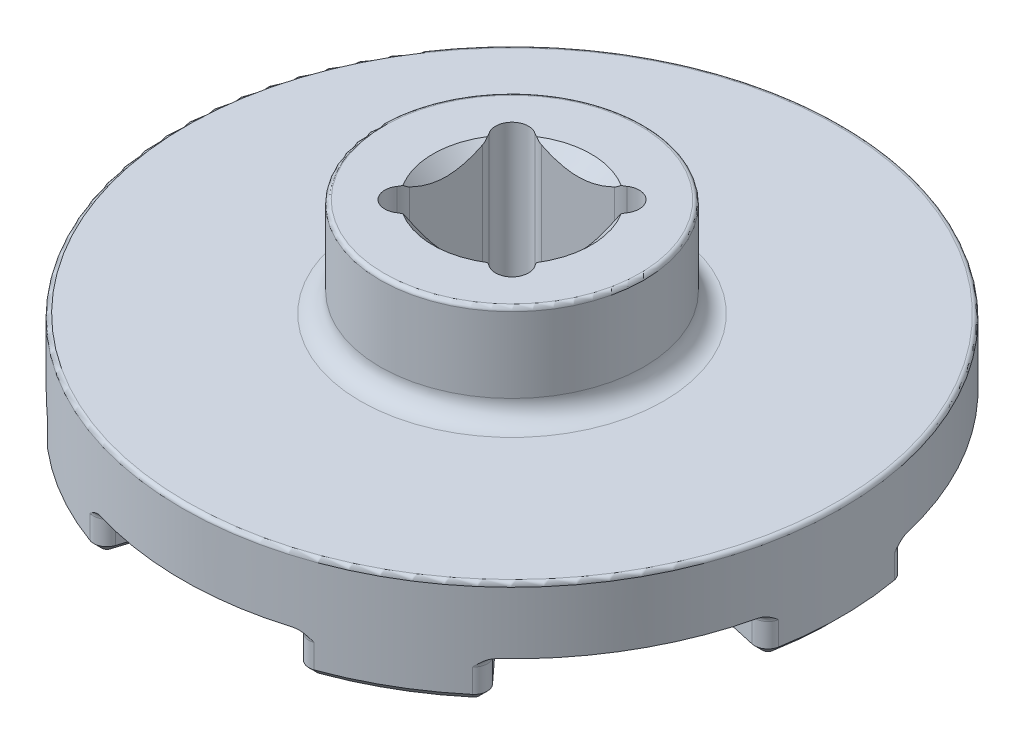
SolidWorks part; units mm, degrees
material "AISI Type S7 Tool Steel"
ref_plane "Front Plane" through (0, 0, 0) normal (0, 0, 1) x (1, 0, 0)
ref_plane "Top Plane" through (0, 0, 0) normal (0, 1, 0) x (1, 0, 0)
ref_plane "Right Plane" through (0, 0, 0) normal (1, 0, 0) x (0, 0, -1)
sketch "Sketch1" plane through (0, 0, 0) normal (0, 0, 1) x (1, 0, 0)
  line L0 (6.35, 31.75) -> (6.35, 0)
  line L1 (6.35, 0) -> (9.525, 0)
  line L2 (9.525, 0) -> (9.525, 15.875)
  line L3 (9.525, 15.875) -> (31.75, 15.875)
  line L4 (31.75, 15.875) -> (31.75, 22.225)
  line L5 (31.75, 22.225) -> (12.7, 22.225)
  line L6 (12.7, 22.225) -> (12.7, 31.75)
  line L7 (12.7, 31.75) -> (6.35, 31.75)
  line L8 (0, 0) -> (0, 31.75) construction
  dimension "D1" = 6.35
  dimension "D2" = 9.525
  dimension "D3" = 31.75
  dimension "D4" = 6.35
  dimension "D5" = 6.35
  dimension "D6" = 15.875
  dimension "D7" = 31.75
revolve "Revolve1" add sketch "Sketch1" angle 360 about L8
chamfer "Chamfer1" distance 1.27 angle 45 1 edges at (0, 31.75, -6.35)
sketch "Sketch3" plane through (0, 15.875, 0) normal (0, -1, 0) x (1, 0, 0)
  line L0 (0, 0) -> (15.875, 27.4963) construction
  line L1 (9.1576, 29.044) -> (3.7808, 11.9911)
  line L2 (8.4942, 9.2698) -> (20.5741, 22.4527)
  line L3 (3.7808, 11.9911) -> (8.4942, 9.2698) construction
  line L4 (0, 0) -> (0, 31.75) construction
  line L5 (9.5474, 30.2805) -> (21.45, 23.4086) construction
  line L8 (29.7317, 6.5914) -> (12.275, 2.7213)
  line L9 (12.275, -2.7213) -> (29.7317, -6.5914)
  line L10 (0, 0) -> (31.75, 0) construction
  line L13 (12.275, 2.7213) -> (12.275, -2.7213) construction
  line L14 (0, 0) -> (27.4963, 15.875) construction
  line L15 (30.9974, 6.872) -> (30.9974, -6.872) construction
  line L18 (20.5741, -22.4527) -> (8.4942, -9.2698)
  line L19 (3.7808, -11.9911) -> (9.1576, -29.044)
  line L20 (0, 0) -> (15.875, -27.4963) construction
  line L21 (8.4942, -9.2698) -> (3.7808, -11.9911) construction
  line L22 (0, 0) -> (27.4963, -15.875) construction
  line L23 (21.45, -23.4086) -> (9.5474, -30.2805) construction
  line L24 (-9.1576, -29.044) -> (-3.7808, -11.9911)
  line L25 (-8.4942, -9.2698) -> (-20.5741, -22.4527)
  line L26 (0, 0) -> (-15.875, -27.4963) construction
  line L27 (-3.7808, -11.9911) -> (-8.4942, -9.2698) construction
  line L28 (0, 0) -> (0, -31.75) construction
  line L29 (-9.5474, -30.2805) -> (-21.45, -23.4086) construction
  line L30 (-29.7317, -6.5914) -> (-12.275, -2.7213)
  line L31 (-12.275, 2.7213) -> (-29.7317, 6.5914)
  line L32 (0, 0) -> (-31.75, 0) construction
  line L33 (-12.275, -2.7213) -> (-12.275, 2.7213) construction
  line L34 (0, 0) -> (-27.4963, -15.875) construction
  line L35 (-30.9974, -6.872) -> (-30.9974, 6.872) construction
  line L36 (-20.5741, 22.4527) -> (-8.4942, 9.2698)
  line L37 (-3.7808, 11.9911) -> (-9.1576, 29.044)
  line L38 (0, 0) -> (-15.875, 27.4963) construction
  line L39 (-8.4942, 9.2698) -> (-3.7808, 11.9911) construction
  line L40 (0, 0) -> (-27.4963, 15.875) construction
  line L41 (-21.45, 23.4086) -> (-9.5474, 30.2805) construction
  line L42 (0, 0) -> (8.4942, 9.2698) construction
  arc A0 (20.456, 24.282) -> (10.8008, 29.8564) centre (0, 0) ccw
  arc A1 (8.4942, 9.2698) -> (3.7808, 11.9911) centre (0, 0) ccw
  circle A2 centre (0, 0) radius 31.75 construction
  arc A3 (20.456, 24.282) -> (20.5741, 22.4527) centre (19.6378, 23.3107) cw
  arc A4 (9.1576, 29.044) -> (10.8008, 29.8564) centre (10.3688, 28.6622) cw
  arc A17 (31.2568, -5.5744) -> (31.2568, 5.5744) centre (0, 0) ccw
  arc A18 (12.275, -2.7213) -> (12.275, 2.7213) centre (0, 0) ccw
  arc A19 (31.2568, -5.5744) -> (29.7317, -6.5914) centre (30.0065, -5.3515) cw
  arc A20 (29.7317, 6.5914) -> (31.2568, 5.5744) centre (30.0065, 5.3515) cw
  arc A21 (10.8008, -29.8564) -> (20.456, -24.282) centre (0, 0) ccw
  arc A22 (3.7808, -11.9911) -> (8.4942, -9.2698) centre (0, 0) ccw
  arc A23 (10.8008, -29.8564) -> (9.1576, -29.044) centre (10.3688, -28.6622) cw
  arc A24 (20.5741, -22.4527) -> (20.456, -24.282) centre (19.6378, -23.3107) cw
  arc A25 (-20.456, -24.282) -> (-10.8008, -29.8564) centre (0, 0) ccw
  arc A26 (-8.4942, -9.2698) -> (-3.7808, -11.9911) centre (0, 0) ccw
  arc A27 (-20.456, -24.282) -> (-20.5741, -22.4527) centre (-19.6378, -23.3107) cw
  arc A28 (-9.1576, -29.044) -> (-10.8008, -29.8564) centre (-10.3688, -28.6622) cw
  arc A29 (-31.2568, 5.5744) -> (-31.2568, -5.5744) centre (0, 0) ccw
  arc A30 (-12.275, 2.7213) -> (-12.275, -2.7213) centre (0, 0) ccw
  arc A31 (-31.2568, 5.5744) -> (-29.7317, 6.5914) centre (-30.0065, 5.3515) cw
  arc A32 (-29.7317, -6.5914) -> (-31.2568, -5.5744) centre (-30.0065, -5.3515) cw
  arc A33 (-10.8008, 29.8564) -> (-20.456, 24.282) centre (0, 0) ccw
  arc A34 (-3.7808, 11.9911) -> (-8.4942, 9.2698) centre (0, 0) ccw
  arc A35 (-10.8008, 29.8564) -> (-9.1576, 29.044) centre (-10.3688, 28.6622) cw
  arc A36 (-20.5741, 22.4527) -> (-20.456, 24.282) centre (-19.6378, 23.3107) cw
  point P9 (15.4987, 26.8445)
  dimension "D1" = 25
  dimension "D3" = 25.146
  dimension "D4" = 1.27
  dimension "D2" = 30
  dimension "D5" = 6
extrude "Boss-Extrude1" add sketch "Sketch3" along normal blind 3.81
sketch "Sketch4" plane through (0, 15.875, 0) normal (0, -1, 0) x (1, 0, 0)
  circle A0 centre (0, 0) radius 12.7
  circle A1 centre (0, 0) radius 7.9375
extrude "Boss-Extrude2" add sketch "Sketch4" along normal up to surface (3.81 mm away) contours A0 | A1 up to face at (12.3126, 12.065, 21.3261)
sketch "Sketch2" plane through (0, 31.75, 0) normal (0, 1, 0) x (1, 0, 0)
  line L1 (-6.35, -6.35) -> (6.35, -6.35)
  line L2 (-6.35, -6.35) -> (-6.35, 6.35)
  line L3 (-6.35, 6.35) -> (6.35, 6.35)
  line L4 (6.35, -6.35) -> (6.35, 6.35)
  line L5 (-6.35, -6.35) -> (6.35, 6.35) construction
  line L6 (-6.35, 6.35) -> (6.35, -6.35) construction
  circle A0 centre (5.334, -5.334) radius 1.5875
  circle A1 centre (-5.334, -5.334) radius 1.5875
  circle A2 centre (-5.334, 5.334) radius 1.5875
  circle A3 centre (5.334, 5.334) radius 1.5875
  point P0 (0, 0)
  dimension "D2" = 3.175
  dimension "D1" = 12.7
  dimension "D3" = 10.668
extrude "Cut-Extrude1" cut sketch "Sketch2" against normal blind 15.875 contours L3 L4 L1 L2 | A0 | A1 | A2 | A3
fillet "Fillet1" radius 1.27 12 edges at (3.819, 13.97, 12.1122) (8.58, 13.97, 9.3634) (8.58, 13.97, -9.3634) (3.819, 13.97, -12.1122) (-3.819, 13.97, 12.1122) (-12.399, 13.97, 2.7488) (-8.58, 13.97, 9.3634) (-8.58, 13.97, -9.3634) (-12.399, 13.97, -2.7488) (-3.819, 13.97, -12.1122) (12.399, 13.97, -2.7488) (12.399, 13.97, 2.7488)
fillet "Fillet2" radius 0.762 42 edges at (14.9865, 15.875, -16.3549) (9.0653, 15.875, -9.4015) (10.9985, 15.875, -6.35) (10.9985, 15.875, 6.35) (9.0653, 15.875, 9.4015) (20.9051, 15.875, 23.3925) (9.806, 15.875, 29.8006) (0, 15.875, 12.7) (3.6093, 15.875, 12.5515) (9.806, 15.875, -29.8006) (6.6705, 15.875, -21.1562) (3.6093, 15.875, -12.5515) (0, 15.875, -12.7) (14.9865, 15.875, 16.3549) (6.6705, 15.875, 21.1562) (30.7111, 15.875, 6.4081) (21.657, 15.875, 4.8012) (12.6746, 15.875, 3.15) (-9.806, 15.875, 29.8006) (-6.6705, 15.875, 21.1562) (-3.6093, 15.875, 12.5515) (20.9051, 15.875, -23.3925) (12.6746, 15.875, -3.15) (30.7111, 15.875, -6.4081) (-9.806, 15.875, -29.8006) (-6.6705, 15.875, -21.1562) (-3.6093, 15.875, -12.5515) (-30.7111, 15.875, -6.4081) (-21.657, 15.875, -4.8012) (-12.6746, 15.875, -3.15) (-20.9051, 15.875, -23.3925) (-14.9865, 15.875, -16.3549) (-9.0653, 15.875, -9.4015) (-20.9051, 15.875, 23.3925) (-14.9865, 15.875, 16.3549) (-9.0653, 15.875, 9.4015) (-30.7111, 15.875, 6.4081) (-21.657, 15.875, 4.8012) (-12.6746, 15.875, 3.15) (21.657, 15.875, -4.8012) (-10.9985, 15.875, -6.35) (-10.9985, 15.875, 6.35)
chamfer "Chamfer2" distance 0.762 angle 45 48 edges at (10.9985, 12.065, -6.35) (9.0653, 12.065, -9.4015) (10.9985, 12.065, 6.35) (9.0653, 12.065, 9.4015) (3.6093, 12.065, -12.5515) (0, 12.065, -12.7) (3.6093, 12.065, 12.5515) (0, 12.065, 12.7) (-6.6705, 12.065, -21.1562) (-3.6093, 12.065, -12.5515) (-9.806, 12.065, -29.8006) (-15.875, 12.065, -27.4963) (-20.9051, 12.065, -23.3925) (6.6705, 12.065, -21.1562) (-14.9865, 12.065, -16.3549) (9.806, 12.065, -29.8006) (-9.0653, 12.065, -9.4015) (15.875, 12.065, -27.4963) (-10.9985, 12.065, -6.35) (20.9051, 12.065, -23.3925) (-12.6746, 12.065, -3.15) (14.9865, 12.065, -16.3549) (-21.657, 12.065, -4.8012) (-30.7111, 12.065, -6.4081) (-31.75, 12.065, 0) (12.6746, 12.065, -3.15) (-30.7111, 12.065, 6.4081) (21.657, 12.065, -4.8012) (-21.657, 12.065, 4.8012) (30.7111, 12.065, -6.4081) (-12.6746, 12.065, 3.15) (31.75, 12.065, 0) (-10.9985, 12.065, 6.35) (30.7111, 12.065, 6.4081) (-9.0653, 12.065, 9.4015) (21.657, 12.065, 4.8012) (-14.9865, 12.065, 16.3549) (12.6746, 12.065, 3.15) (-20.9051, 12.065, 23.3925) (-15.875, 12.065, 27.4963) (-9.806, 12.065, 29.8006) (14.9865, 12.065, 16.3549) (-6.6705, 12.065, 21.1562) (20.9051, 12.065, 23.3925) (-3.6093, 12.065, 12.5515) (15.875, 12.065, 27.4963) (9.806, 12.065, 29.8006) (6.6705, 12.065, 21.1562)
fillet "Fillet3" radius 0.381 5 edges at (0, 31.75, -12.7) (0, 22.225, -31.75) (0, 0, -6.35) (0, 0, -9.525) (0, 12.065, 9.525)
fillet "Fillet4" radius 1.905 1 edges at (0, 22.225, -12.7)
fillet "Fillet5" radius 1.5875 8 edges at (-4.1142, 23.7857, 6.35) (-6.35, 23.7857, 4.1142) (-6.35, 23.7857, -4.1142) (-4.1142, 23.7857, -6.35) (4.1142, 23.7857, -6.35) (6.35, 23.7857, -4.1142) (6.35, 23.7857, 4.1142) (4.1142, 23.7857, 6.35)
